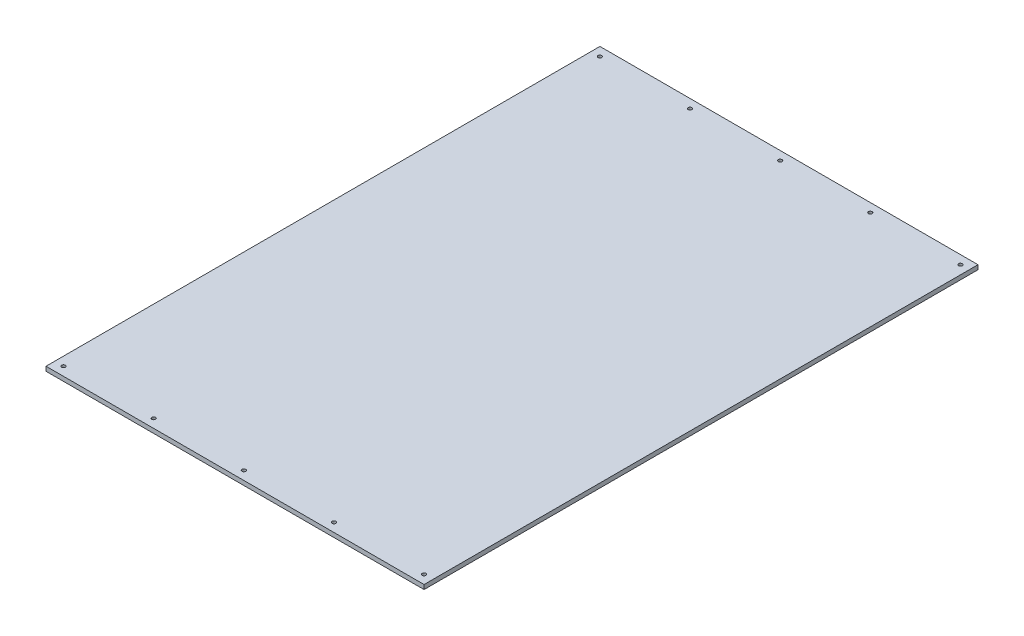
SolidWorks part; units mm, degrees
ref_plane "Front Plane" through (0, 0, 0) normal (0, 0, 1) x (1, 0, 0)
ref_plane "Top Plane" through (0, 0, 0) normal (0, 1, 0) x (1, 0, 0)
ref_plane "Right Plane" through (0, 0, 0) normal (1, 0, 0) x (0, 0, -1)
sketch "Sketch1" plane through (0, 0, 0) normal (0, 1, 0) x (1, 0, 0)
  line L1 (-215, 315) -> (215, 315)
  line L2 (-215, 315) -> (-215, -315)
  line L3 (-215, -315) -> (215, -315)
  line L4 (215, 315) -> (215, -315)
  line L5 (-215, 315) -> (215, -315) construction
  line L6 (-215, -315) -> (215, 315) construction
  point P0 (0, 0)
  dimension "D1" = 630
  dimension "D2" = 430
extrude "Boss-Extrude1" add sketch "Sketch1" along normal blind 5
sketch "Sketch2" plane through (0, 5, 0) normal (0, 1, 0) x (1, 0, 0)
  line L0 (-215, 315) -> (-215, 305) construction
  line L1 (-215, 315) -> (-215, -315) construction
  line L2 (-215, 305) -> (215, 305) construction
  line L3 (-2.75, 0) -> (2.75, 0) construction
  circle A0 centre (0, 305) radius 2.1
  circle A1 centre (102.5, 305) radius 2.1
  circle A2 centre (205, 305) radius 2.1
  circle A3 centre (-102.5, 305) radius 2.1
  circle A4 centre (-205, 305) radius 2.1
  circle A5 centre (205, -305) radius 2.1
  circle A6 centre (102.5, -305) radius 2.1
  circle A7 centre (0, -305) radius 2.1
  circle A8 centre (-102.5, -305) radius 2.1
  circle A9 centre (-205, -305) radius 2.1
  dimension "D3" = 4.2
  dimension "D4" = 4.2
  dimension "D5" = 4.2
  dimension "D6" = 4.2
  dimension "D7" = 4.2
  dimension "D1" = 10
  dimension "D2" = 430
  dimension "D8" = 10
  dimension "D9" = 102.5
  dimension "D10" = 10
  dimension "D11" = 102.5
extrude "Cut-Extrude1" cut sketch "Sketch2" against normal blind 5
